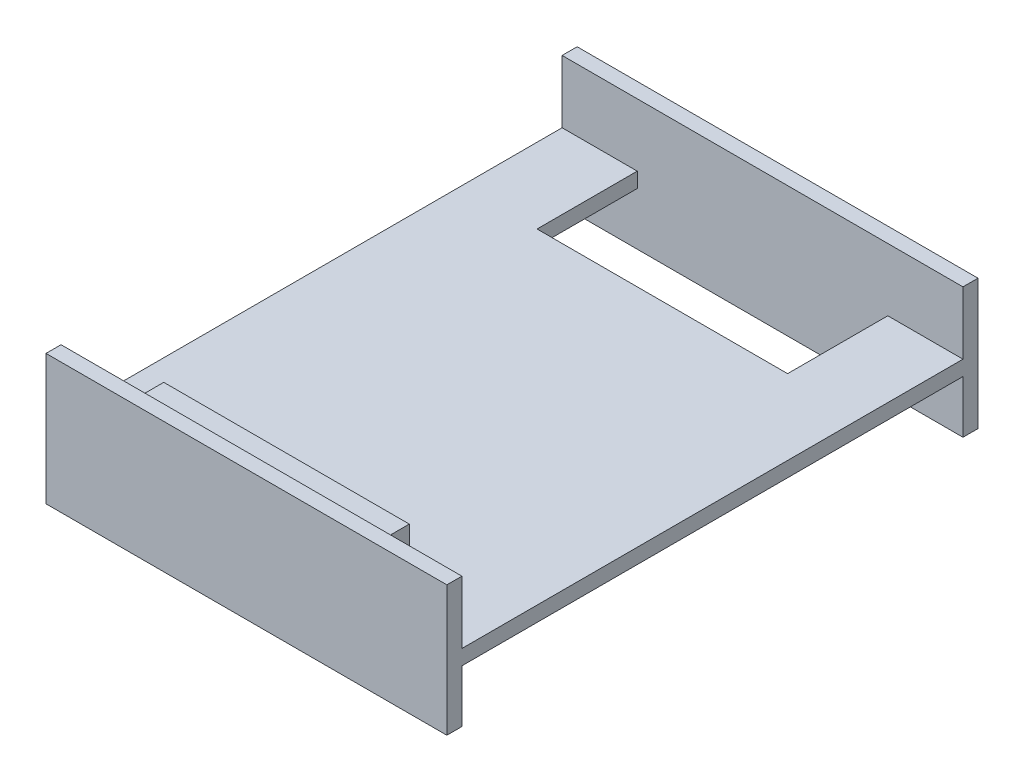
SolidWorks part; units mm, degrees
ref_plane "前视基准面" through (0, 0, 0) normal (0, 0, 1) x (1, 0, 0)
ref_plane "上视基准面" through (0, 0, 0) normal (0, 1, 0) x (1, 0, 0)
ref_plane "右视基准面" through (0, 0, 0) normal (1, 0, 0) x (0, 0, -1)
other "Configuration Table"
sketch "草图1" plane through (0, 0, 0) normal (0, 1, 0) x (1, 0, 0)
  line L1 (32, 0) -> (32, 40)
  line L3 (0, 40) -> (0, 0)
  line L4 (0, -1.2) -> (0, 0)
  line L5 (0, -1.2) -> (32, -1.2)
  line L6 (32, -1.2) -> (32, 0)
  line L7 (0, 40) -> (0, 41.2)
  line L8 (0, 41.2) -> (32, 41.2)
  line L9 (32, 41.2) -> (32, 40)
extrude "凸台-拉伸-中间层" add sketch "草图1" along normal blind 1.2
sketch "草图2" plane through (0, 1.2, 0) normal (0, 1, 0) x (1, 0, 0)
  line L0 (0, 0) -> (0, -1.2)
  line L1 (0, -1.2) -> (32, -1.2)
  line L2 (32, -1.2) -> (32, 0)
  line L3 (32, -1.2) -> (32, 41.2) construction
  line L4 (32, 0) -> (0, 0)
  line L5 (0, 41.2) -> (32, 41.2)
  line L6 (32, 41.2) -> (32, 40)
  line L7 (32, 40) -> (0, 40)
  line L8 (0, 41.2) -> (0, -1.2) construction
  line L9 (0, 40) -> (0, 41.2)
extrude "凸台-拉伸-PCB侧上下挡板" add sketch "草图2" along normal blind 5
sketch "草图3" plane through (0, 1.2, 0) normal (0, 1, 0) x (1, 0, 0)
  line L0 (32, 0) -> (0, 0) construction
  line L1 (16, 0) -> (25.8, 0)
  line L2 (32, 0) -> (0, 0) construction
  line L3 (25.8, 0) -> (25.8, 2)
  line L4 (16, 0) -> (6.2, 0)
  line L5 (6.2, 0) -> (6.2, 2)
  line L6 (6.2, 2) -> (25.8, 2)
  point P0 (16, 0)
extrude "凸台-拉伸-PCB侧下方卡槽" add sketch "草图3" along normal blind 4.5
sketch "草图4" plane through (0, 1.2, 0) normal (0, 1, 0) x (1, 0, 0)
  line L0 (0, 40) -> (32, 40) construction
  line L1 (16, 40) -> (26, 40)
  line L2 (0, 40) -> (32, 40) construction
  line L3 (16, 40) -> (6, 40)
  line L4 (6, 40) -> (6, 32)
  line L5 (6, 32) -> (26, 32)
  line L6 (26, 32) -> (26, 40)
  point P0 (16, 40)
extrude "切除-拉伸-穿线孔" cut sketch "草图4" against normal up to next
sketch "草图5" plane through (0, 0, 0) normal (0, -1, 0) x (1, 0, 0)
  line L0 (0, 1.2) -> (0, 0)
  line L1 (0, 0) -> (32, 0)
  line L3 (0, -40) -> (32, -40)
  line L5 (32, 0) -> (32, 1.2)
  line L6 (32, 1.2) -> (0, 1.2)
  line L7 (0, -40) -> (0, -41.2)
  line L8 (0, -41.2) -> (32, -41.2)
  line L9 (32, -41.2) -> (32, -40)
extrude "凸台-拉伸-电池侧上下挡板" add sketch "草图5" along normal blind 4.2
